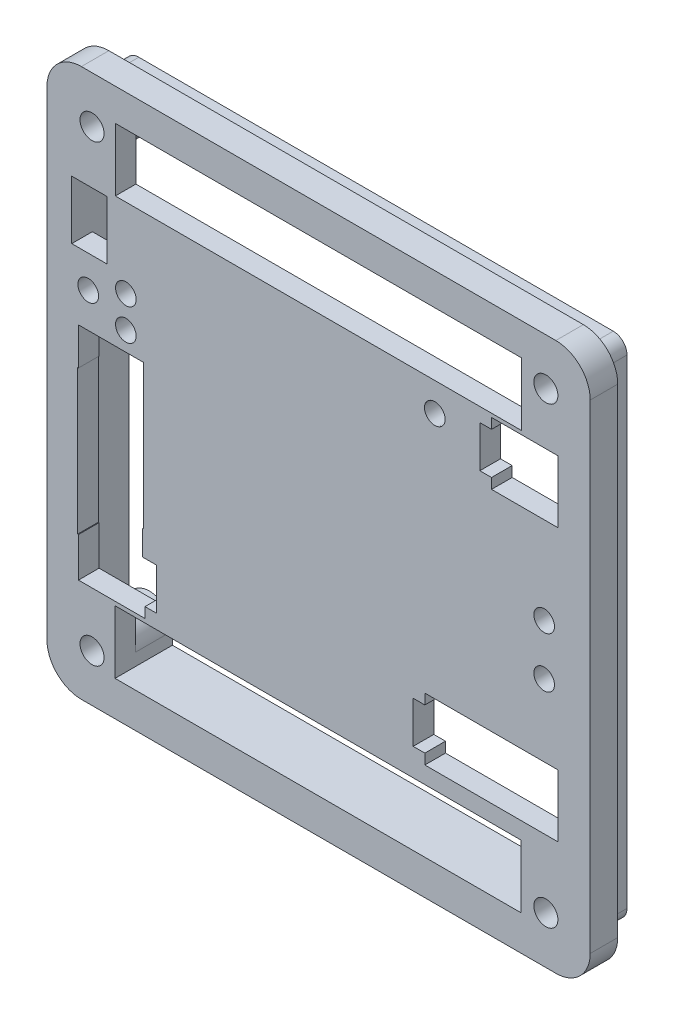
SolidWorks part; units mm, degrees
note: The reader was unsure of these and kept them because the rebuilt part matched: shared geometry of "Sketch9<3>".
ref_plane "Front Plane" through (0, 0, 0) normal (0, 0, 1) x (1, 0, 0)
ref_plane "Top Plane" through (0, 0, 0) normal (0, 1, 0) x (1, 0, 0)
ref_plane "Right Plane" through (0, 0, 0) normal (1, 0, 0) x (0, 0, -1)
sketch "Sketch1" plane through (0, 0, 0) normal (0, 0, 1) x (1, 0, 0)
  line L0 (188.15, -67.0655) -> (188.15, -73.1255)
  line L1 (127.6652, -102.1209) -> (127.6652, -110.3509)
  line L2 (127.6652, -110.3509) -> (137.1152, -110.3509)
  line L3 (137.1152, -110.3509) -> (137.1152, -89.3909)
  line L4 (127.9652, -97.6209) -> (127.9652, -102.1209) construction
  line L5 (137.1152, -89.3909) -> (127.6652, -89.3909)
  line L6 (127.6652, -89.3909) -> (127.6652, -97.6209)
  line L7 (127.6652, -97.6209) -> (127.6652, -102.1209)
  line L8 (128.2, -130.9) -> (197.2, -130.9)
  line L9 (202.2, -125.9) -> (202.2, -56.2)
  line L10 (197.2, -51.2) -> (128.2, -51.2)
  line L11 (123.2, -56.2) -> (123.2, -125.9)
  line L15 (188.15, -73.1255) -> (189.05, -73.1255)
  line L16 (189.05, -73.1255) -> (189.85, -73.1255)
  line L17 (189.85, -73.1255) -> (190.15, -73.1255)
  line L18 (190.15, -73.1255) -> (190.15, -74.3255)
  line L31 (127.9652, -102.1209) -> (127.9652, -110.0509)
  line L32 (160.412, -56.033) -> (133.432, -56.033) construction
  line L33 (133.432, -56.033) -> (133.432, -64.883) construction
  line L34 (133.432, -64.883) -> (191.892, -64.883) construction
  line L35 (191.892, -64.883) -> (191.892, -56.033) construction
  line L36 (191.892, -56.033) -> (164.912, -56.033) construction
  line L45 (190.15, -74.3255) -> (197.25, -74.3255)
  line L46 (197.25, -74.3255) -> (197.25, -65.8655)
  line L47 (197.25, -65.8655) -> (190.15, -65.8655)
  line L49 (190.15, -65.8655) -> (190.15, -67.0655)
  line L50 (190.15, -67.0655) -> (189.85, -67.0655)
  line L51 (189.85, -67.0655) -> (189.05, -67.0655)
  line L52 (189.05, -67.0655) -> (188.15, -67.0655)
  line L53 (133.132, -55.733) -> (192.192, -55.733)
  line L62 (188.15, -67.0655) -> (186.15, -67.0655)
  line L68 (188.15, -67.0655) -> (188.15, -73.1255)
  line L76 (188.15, -73.1255) -> (186.15, -73.1255)
  line L82 (186.15, -67.0655) -> (186.15, -73.1255)
  line L90 (127.9652, -110.0509) -> (136.8152, -110.0509)
  line L96 (136.8152, -110.0509) -> (136.8152, -89.6909)
  line L99 (136.8152, -89.6909) -> (127.9652, -89.6909)
  line L110 (127.9652, -89.6909) -> (127.9652, -97.6209)
  line L117 (127.9652, -97.6209) -> (237.023, -182.4747)
  line L118 (237.023, -182.4747) -> (233.3202, -188.1423)
  line L120 (233.3202, -188.1423) -> (228.0042, -184.6692)
  line L122 (228.0042, -184.6692) -> (237.871, -169.5667)
  line L123 (237.871, -169.5667) -> (243.1871, -173.0398)
  line L125 (131.6, -68.5) -> (131.6, -67.5) construction
  line L126 (131.6, -67.5) -> (131.65, -67.5) construction
  line L127 (131.65, -67.5) -> (131.65, -67) construction
  line L128 (131.65, -67) -> (131.6, -67) construction
  line L129 (131.6, -67) -> (131.6, -66) construction
  line L130 (131.6, -66) -> (130.1, -66) construction
  line L135 (130.1, -73.9) -> (131.6, -73.9) construction
  line L136 (131.6, -73.9) -> (131.6, -71.4) construction
  line L140 (127.1, -73.9) -> (129.3, -73.9) construction
  line L146 (129.3, -66) -> (127.1, -66) construction
  line L147 (127.1, -66) -> (127.1, -73.9) construction
  line L148 (188.45, -67.3655) -> (188.45, -72.8255) construction
  line L149 (188.45, -72.8255) -> (189.05, -72.8255) construction
  line L150 (189.05, -67.3655) -> (188.45, -67.3655) construction
  line L151 (189.05, -72.8255) -> (189.85, -72.8255) construction
  line L152 (189.85, -67.3655) -> (189.05, -67.3655) construction
  line L153 (189.85, -72.8255) -> (190.45, -72.8255) construction
  line L154 (131.6, -68.5) -> (131.6, -71.4) construction
  line L155 (190.45, -67.3655) -> (189.85, -67.3655) construction
  line L156 (190.45, -74.0255) -> (196.95, -74.0255) construction
  line L157 (196.95, -74.0255) -> (196.95, -66.1655) construction
  line L158 (196.95, -66.1655) -> (190.45, -66.1655) construction
  line L159 (190.45, -66.1655) -> (190.45, -67.3655) construction
  line L160 (130.1, -73.9) -> (129.3, -73.9) construction
  line L161 (190.45, -72.8255) -> (190.45, -74.0255) construction
  line L162 (178.75, -106.9275) -> (178.75, -112.3875) construction
  line L163 (178.75, -112.3875) -> (179.35, -112.3875) construction
  line L164 (179.35, -106.9275) -> (178.75, -106.9275) construction
  line L165 (179.35, -112.3875) -> (180.15, -112.3875) construction
  line L166 (180.15, -106.9275) -> (179.35, -106.9275) construction
  line L167 (180.15, -112.3875) -> (180.75, -112.3875) construction
  line L168 (129.3, -66) -> (130.1, -66) construction
  line L169 (180.75, -106.9275) -> (180.15, -106.9275) construction
  line L170 (180.75, -113.5875) -> (187.25, -113.5875) construction
  line L171 (187.25, -113.5875) -> (187.25, -105.7275) construction
  line L172 (187.25, -105.7275) -> (180.75, -105.7275) construction
  line L173 (180.75, -105.7275) -> (180.75, -106.9275) construction
  line L174 (243.1871, -173.0398) -> (239.4842, -178.7074)
  line L175 (180.75, -112.3875) -> (180.75, -113.5875) construction
  line L176 (188.45, -106.9275) -> (188.45, -112.3875) construction
  line L177 (188.45, -112.3875) -> (189.05, -112.3875) construction
  line L178 (189.05, -106.9275) -> (188.45, -106.9275) construction
  line L179 (189.05, -112.3875) -> (189.85, -112.3875) construction
  line L180 (189.85, -106.9275) -> (189.05, -106.9275) construction
  line L181 (189.85, -112.3875) -> (190.45, -112.3875) construction
  line L182 (133.432, -56.033) -> (191.892, -56.033) construction
  line L183 (190.45, -106.9275) -> (189.85, -106.9275) construction
  line L184 (190.45, -113.5875) -> (196.95, -113.5875) construction
  line L185 (196.95, -113.5875) -> (196.95, -105.7275) construction
  line L186 (196.95, -105.7275) -> (190.45, -105.7275) construction
  line L187 (190.45, -105.7275) -> (190.45, -106.9275) construction
  line L188 (133.432, -56.033) -> (133.432, -64.883) construction
  line L189 (190.45, -112.3875) -> (190.45, -113.5875) construction
  line L190 (135.45, -108.8275) -> (134.85, -108.8275) construction
  line L191 (133.432, -64.883) -> (191.892, -64.883) construction
  line L192 (134.85, -114.2875) -> (135.45, -114.2875) construction
  line L193 (136.85, -114.2875) -> (136.85, -108.8275) construction
  line L194 (136.85, -108.8275) -> (136.25, -108.8275) construction
  line L195 (136.25, -114.2875) -> (136.85, -114.2875) construction
  line L196 (136.25, -108.8275) -> (135.45, -108.8275) construction
  line L197 (135.45, -114.2875) -> (136.25, -114.2875) construction
  line L198 (134.85, -107.6275) -> (128.35, -107.6275) construction
  line L199 (128.35, -107.6275) -> (128.35, -115.4875) construction
  line L200 (128.35, -115.4875) -> (134.85, -115.4875) construction
  line L201 (134.85, -115.4875) -> (134.85, -114.2875) construction
  line L202 (191.892, -56.033) -> (191.892, -64.883) construction
  line L203 (134.85, -108.8275) -> (134.85, -107.6275) construction
  line L204 (164.875, -125.655) -> (191.855, -125.655) construction
  line L205 (191.855, -125.655) -> (191.855, -116.805) construction
  line L206 (191.855, -116.805) -> (133.395, -116.805) construction
  line L207 (133.395, -116.805) -> (133.395, -125.655) construction
  line L208 (133.395, -125.655) -> (160.375, -125.655) construction
  line L216 (160.375, -125.655) -> (164.875, -125.655) construction
  line L217 (160.412, -56.033) -> (164.875, -56.033) construction
  line L218 (133.132, -55.733) -> (133.132, -65.183)
  line L219 (133.132, -65.183) -> (192.192, -65.183)
  line L220 (192.192, -65.183) -> (192.192, -55.733)
  line L221 (239.4842, -178.7074) -> (127.9652, -102.1209)
  line L222 (126.8, -65.7) -> (126.8, -74.2)
  line L223 (126.8, -74.2) -> (129.3, -74.2)
  line L224 (130.1, -74.2) -> (129.3, -74.2)
  line L225 (130.1, -74.2) -> (131.9, -74.2)
  line L226 (131.9, -74.2) -> (131.9, -71.4)
  line L227 (131.9, -68.5) -> (131.9, -71.4)
  line L228 (131.9, -68.5) -> (131.9, -67.8)
  line L229 (131.9, -67.8) -> (131.95, -67.8)
  line L230 (131.95, -67.8) -> (131.95, -66.7)
  line L231 (131.95, -66.7) -> (131.9, -66.7)
  line L232 (131.9, -66.7) -> (131.9, -65.7)
  line L233 (131.9, -65.7) -> (130.1, -65.7)
  line L234 (129.3, -65.7) -> (130.1, -65.7)
  line L235 (129.3, -65.7) -> (126.8, -65.7)
  line L236 (128.05, -107.3275) -> (128.05, -115.7875)
  line L237 (128.05, -115.7875) -> (135.15, -115.7875)
  line L238 (135.15, -115.7875) -> (135.15, -114.5875)
  line L239 (135.15, -114.5875) -> (135.45, -114.5875)
  line L240 (135.45, -114.5875) -> (136.25, -114.5875)
  line L241 (136.25, -114.5875) -> (137.15, -114.5875)
  line L242 (137.15, -114.5875) -> (137.15, -108.5275)
  line L243 (137.15, -108.5275) -> (136.25, -108.5275)
  line L244 (136.25, -108.5275) -> (135.45, -108.5275)
  line L245 (135.45, -108.5275) -> (135.15, -108.5275)
  line L246 (135.15, -108.5275) -> (135.15, -107.3275)
  line L247 (135.15, -107.3275) -> (128.05, -107.3275)
  line L248 (180.45, -113.8875) -> (187.55, -113.8875)
  line L250 (187.55, -105.4275) -> (180.45, -105.4275)
  line L251 (180.45, -105.4275) -> (180.45, -106.6275)
  line L252 (180.45, -106.6275) -> (180.15, -106.6275)
  line L253 (180.15, -106.6275) -> (179.35, -106.6275)
  line L254 (179.35, -106.6275) -> (178.45, -106.6275)
  line L255 (178.45, -106.6275) -> (178.45, -112.6875)
  line L256 (178.45, -112.6875) -> (179.35, -112.6875)
  line L257 (179.35, -112.6875) -> (180.15, -112.6875)
  line L258 (180.15, -112.6875) -> (180.45, -112.6875)
  line L259 (180.45, -112.6875) -> (180.45, -113.8875)
  line L267 (190.15, -113.8875) -> (197.25, -113.8875)
  line L268 (197.25, -113.8875) -> (197.25, -105.4275)
  line L269 (197.25, -105.4275) -> (190.15, -105.4275)
  line L272 (192.155, -116.505) -> (133.095, -116.505)
  line L273 (133.095, -116.505) -> (133.095, -125.955)
  line L274 (133.095, -125.955) -> (160.375, -125.955)
  line L275 (160.375, -125.955) -> (164.875, -125.955)
  line L276 (164.875, -125.955) -> (192.155, -125.955)
  line L277 (192.155, -125.955) -> (192.155, -116.505)
  line L278 (187.55, -105.4275) -> (190.15, -105.4275)
  line L279 (190.15, -113.8875) -> (187.55, -113.8875)
  line L280 (127.9652, -102.1209) -> (127.9652, -110.0509) construction
  line L281 (190.15, -105.4275) -> (190.15, -106.6275) construction
  line L282 (190.15, -106.6275) -> (189.85, -106.6275) construction
  line L283 (189.85, -106.6275) -> (189.05, -106.6275) construction
  line L284 (189.05, -106.6275) -> (188.15, -106.6275) construction
  line L285 (188.15, -106.6275) -> (188.15, -112.6875) construction
  line L286 (190.15, -112.6875) -> (190.15, -113.8875) construction
  line L287 (189.85, -112.6875) -> (190.15, -112.6875) construction
  line L288 (189.05, -112.6875) -> (189.85, -112.6875) construction
  line L289 (188.15, -112.6875) -> (189.05, -112.6875) construction
  line L290 (187.55, -113.8875) -> (187.55, -105.4275) construction
  line L291 (178.45, -106.6275) -> (176.45, -106.6275)
  line L292 (178.45, -106.6275) -> (178.45, -112.6875)
  line L293 (178.45, -112.6875) -> (176.45, -112.6875)
  line L294 (176.45, -106.6275) -> (176.45, -112.6875)
  line L295 (137.15, -108.5275) -> (139.15, -108.5275)
  line L296 (137.15, -108.5275) -> (137.15, -114.5875)
  line L297 (137.15, -114.5875) -> (139.15, -114.5875)
  line L298 (139.15, -108.5275) -> (139.15, -114.5875)
  line L299 (127.9652, -110.0509) -> (136.8152, -110.0509) construction
  line L300 (192.192, -55.733) -> (164.912, -55.733) construction
  line L301 (160.412, -55.733) -> (133.132, -55.733) construction
  line L302 (136.8152, -110.0509) -> (136.8152, -89.6909) construction
  line L303 (136.8152, -89.6909) -> (127.9652, -89.6909) construction
  line L304 (127.9652, -89.6909) -> (127.9652, -97.6209) construction
  arc A8 (197.2, -130.9) -> (202.2, -125.9) centre (197.2, -125.9) ccw
  arc A9 (202.2, -56.2) -> (197.2, -51.2) centre (197.2, -56.2) ccw
  arc A10 (128.2, -51.2) -> (123.2, -56.2) centre (128.2, -56.2) ccw
  arc A11 (123.2, -125.9) -> (128.2, -130.9) centre (128.2, -125.9) ccw
  circle A14 centre (195.5, -94.675) radius 0.8 construction
  circle A15 centre (195.5, -87.325) radius 0.8 construction
  circle A16 centre (129.2, -78.87) radius 0.8 construction
  circle A17 centre (195.75, -124) radius 1.575 construction
  circle A18 centre (195.75, -58) radius 1.575 construction
  circle A19 centre (129.75, -58) radius 1.575 construction
  circle A21 centre (129.75, -124) radius 1.575 construction
  circle A22 centre (195.5, -94.675) radius 1.1
  circle A23 centre (195.5, -87.325) radius 1.1
  circle A24 centre (129.2, -78.87) radius 1.1
  circle A25 centre (129.75, -58) radius 1.75
  circle A26 centre (129.75, -124) radius 1.75
  circle A27 centre (195.75, -124) radius 1.75
  circle A28 centre (195.75, -58) radius 1.75
  dimension "D8" = 3.5
  dimension "D4" = 2
  dimension "D5" = 2
  dimension "D7" = 2
  dimension "D1" = 0
  dimension "D2" = 0.3
  dimension "D3" = 0.3
  dimension "D6" = 0.3
extrude "Boss-Extrude1" add sketch "Sketch1" along normal blind 3 contours L11 A11 L8 A8 L9 A9 L10 A10 A28 A27 A26 A25 A24 A23 A22 L295 L298 L297 L241 L240 L239 L238 L237 L236 L247 L246 L245 L244 L243 L82 L62 L52 L51 L50 L49 L47 L46 L45 L18 L17 L16 L15
sketch "Sketch2" plane through (0, 0, 0) normal (0, 0, -1) x (-1, 0, 0)
  line L1 (-192.192, -58) -> (-192.192, -55.733)
  line L3 (-133.132, -58) -> (-133.132, -55.733)
  line L4 (-123.2, -125.9) -> (-123.2, -56.2)
  line L5 (-128.2, -51.2) -> (-197.2, -51.2)
  line L6 (-202.2, -56.2) -> (-202.2, -125.9)
  line L7 (-197.2, -130.9) -> (-128.2, -130.9)
  line L8 (-123.2, -125.9) -> (-123.2, -116.505)
  line L9 (-128.2, -51.2) -> (-133.132, -51.2)
  line L10 (-202.2, -56.2) -> (-202.2, -65.183)
  line L11 (-197.2, -130.9) -> (-192.155, -130.9)
  line L13 (-133.095, -124) -> (-133.095, -125.955)
  line L15 (-192.155, -124) -> (-192.155, -125.955)
  line L16 (-192.192, -51.2) -> (-197.2, -51.2)
  line L17 (-202.2, -116.505) -> (-202.2, -125.9)
  line L18 (-123.2, -65.183) -> (-123.2, -56.2)
  line L19 (-133.095, -130.9) -> (-128.2, -130.9)
  line L20 (-192.192, -55.733) -> (-133.132, -55.733)
  line L21 (-127.0358, -125.955) -> (-126.8, -125.955)
  line L23 (-126.8, -122.4231) -> (-126.8, -59.6539)
  line L24 (-126.8, -125.955) -> (-126.8, -125.5769)
  line L26 (-197.25, -61.2264) -> (-197.25, -120.7329)
  line L27 (-202.2, -65.183) -> (-202.2, -116.505)
  line L28 (-123.2, -65.183) -> (-123.2, -116.505)
  line L29 (-192.155, -125.955) -> (-133.095, -125.955)
  line L30 (-192.155, -130.9) -> (-133.095, -130.9)
  line L31 (-192.192, -51.2) -> (-133.132, -51.2)
  arc A0 (-197.25, -61.2264) -> (-192.192, -58) centre (-195.75, -58) ccw
  arc A2 (-127.0358, -125.955) -> (-126.8, -125.5769) centre (-129.75, -124) ccw
  arc A3 (-133.132, -58) -> (-126.8, -59.6539) centre (-129.75, -58) ccw
  arc A4 (-123.2, -56.2) -> (-128.2, -51.2) centre (-128.2, -56.2) ccw
  arc A5 (-197.2, -51.2) -> (-202.2, -56.2) centre (-197.2, -56.2) ccw
  arc A6 (-202.2, -125.9) -> (-197.2, -130.9) centre (-197.2, -125.9) ccw
  arc A7 (-128.2, -130.9) -> (-123.2, -125.9) centre (-128.2, -125.9) ccw
  arc A8 (-123.2, -56.2) -> (-128.2, -51.2) centre (-128.2, -56.2) ccw
  arc A9 (-197.2, -51.2) -> (-202.2, -56.2) centre (-197.2, -56.2) ccw
  arc A10 (-202.2, -125.9) -> (-197.2, -130.9) centre (-197.2, -125.9) ccw
  arc A11 (-128.2, -130.9) -> (-123.2, -125.9) centre (-128.2, -125.9) ccw
  arc A12 (-192.155, -124) -> (-197.25, -120.7329) centre (-195.75, -124) ccw
  arc A13 (-126.8, -122.4231) -> (-133.095, -124) centre (-129.75, -124) ccw
  circle A15 centre (-195.75, -58) radius 1.75 construction
  circle A16 centre (-129.75, -58) radius 1.75 construction
  circle A17 centre (-129.75, -124) radius 1.75 construction
  circle A18 centre (-195.75, -124) radius 1.75 construction
  circle A19 centre (-195.75, -58) radius 1.75
  circle A20 centre (-129.75, -58) radius 1.75
  circle A21 centre (-129.75, -124) radius 1.75
  circle A22 centre (-195.75, -124) radius 1.75
  point P39 (-197.25, -91.05)
  point P42 (-162.7, -55.733)
  point P45 (-126.8, -88.6775)
  point P52 (-162.7, -125.955)
  dimension "D1" = 0
extrude "Boss-Extrude2" add sketch "Sketch2" along normal blind 6.15
sketch "Sketch3" plane through (0, -51.2, 0) normal (0, 1, 0) x (1, 0, 0)
  line L0 (197.2, -3) -> (128.2, -3) construction
  line L1 (45.1071, 1) -> (280.2929, 1)
  line L2 (45.1071, 1) -> (45.1071, -7)
  line L3 (45.1071, -7) -> (280.2929, -7)
  line L4 (280.2929, 1) -> (280.2929, -7)
  line L5 (45.1071, 1) -> (280.2929, -7) construction
  line L6 (45.1071, -7) -> (280.2929, 1) construction
  point P0 (162.7, -3)
  dimension "D1" = 4
sketch "Sketch4" plane through (0, 0, -6.15) normal (0, 0, 1) x (1, 0, 0)
  line L8 (96.5451, -180.9483) -> (273.7958, -180.9483)
  line L9 (96.5451, -180.9483) -> (96.5451, -1.9529)
  line L10 (96.5451, -1.9529) -> (273.7958, -1.9529)
  line L17 (126.2, -56.2) -> (126.2, -125.9)
  line L18 (197.2, -54.2) -> (128.2, -54.2)
  line L19 (199.2, -125.9) -> (199.2, -56.2)
  line L20 (128.2, -127.9) -> (197.2, -127.9)
  line L21 (126.2, -56.2) -> (126.2, -125.9)
  line L22 (197.2, -54.2) -> (128.2, -54.2)
  line L23 (199.2, -125.9) -> (199.2, -56.2)
  line L24 (128.2, -127.9) -> (197.2, -127.9)
  line L25 (273.7958, -180.9483) -> (273.7958, -1.9529)
  arc A8 (126.2, -125.9) -> (128.2, -127.9) centre (128.2, -125.9) ccw
  arc A9 (128.2, -54.2) -> (126.2, -56.2) centre (128.2, -56.2) ccw
  arc A10 (199.2, -56.2) -> (197.2, -54.2) centre (197.2, -56.2) ccw
  arc A11 (197.2, -127.9) -> (199.2, -125.9) centre (197.2, -125.9) ccw
  arc A12 (126.2, -125.9) -> (128.2, -127.9) centre (128.2, -125.9) ccw
  arc A13 (128.2, -54.2) -> (126.2, -56.2) centre (128.2, -56.2) ccw
  arc A14 (199.2, -56.2) -> (197.2, -54.2) centre (197.2, -56.2) ccw
  arc A15 (197.2, -127.9) -> (199.2, -125.9) centre (197.2, -125.9) ccw
  dimension "D1" = 3
extrude "Cut-Extrude2" cut sketch "Sketch4" along normal blind 5.15
sketch "Sketch5" plane through (0, 0, 3) normal (0, 0, 1) x (1, 0, 0)
  line L0 (128.06, -92.17) -> (128.06, -96.67) construction
  line L1 (127.76, -92.17) -> (127.76, -96.67)
  line L2 (127.76, -96.67) -> (127.76, -104.9)
  line L3 (127.76, -104.9) -> (137.21, -104.9)
  line L4 (137.21, -104.9) -> (137.21, -83.94)
  line L5 (137.21, -83.94) -> (127.76, -83.94)
  line L6 (127.76, -83.94) -> (127.76, -92.17)
  line L12 (128.06, -96.67) -> (128.06, -104.6)
  line L13 (128.06, -104.6) -> (136.91, -104.6)
  line L14 (136.91, -104.6) -> (136.91, -84.24)
  line L15 (136.91, -84.24) -> (128.06, -84.24)
  line L16 (128.06, -84.24) -> (128.06, -92.17)
  line L17 (128.06, -92.17) -> (129.31, -92.17)
  line L18 (129.31, -92.17) -> (129.31, -85.4)
  line L19 (129.31, -85.4) -> (135.66, -85.4)
  line L20 (135.66, -85.4) -> (135.66, -103.44)
  line L21 (135.66, -103.44) -> (129.31, -103.44)
  line L22 (129.31, -103.44) -> (129.31, -96.67)
  line L23 (129.31, -96.67) -> (128.06, -96.67)
  line L24 (128.06, -96.67) -> (128.06, -104.6) construction
  line L25 (128.06, -104.6) -> (136.91, -104.6) construction
  line L26 (136.91, -104.6) -> (136.91, -84.24) construction
  line L27 (136.91, -84.24) -> (128.06, -84.24) construction
  line L28 (128.06, -84.24) -> (128.06, -92.17) construction
  dimension "D1" = 0
  dimension "D2" = 0.3
extrude "Cut-Extrude3" cut sketch "Sketch5" against normal through all both and the other way through all
sketch "Sketch6" plane through (0, 0, 3) normal (0, 0, 1) x (1, 0, 0)
  line L3 (190.15, -65.8655) -> (189.65, -65.8655)
  line L4 (190.15, -65.8655) -> (190.15, -74.3255)
  line L5 (190.15, -74.3255) -> (189.65, -74.3255)
  line L6 (189.65, -65.8655) -> (189.65, -74.3255)
  line L7 (180.45, -105.4275) -> (179.95, -105.4275)
  line L8 (180.45, -105.4275) -> (180.45, -113.8875)
  line L9 (180.45, -113.8875) -> (179.95, -113.8875)
  line L10 (179.95, -105.4275) -> (179.95, -113.8875)
  line L11 (135.15, -115.7875) -> (135.65, -115.7875)
  line L12 (135.15, -115.7875) -> (135.15, -107.6212)
  line L13 (135.15, -107.6212) -> (135.65, -107.6212)
  line L14 (135.65, -115.7875) -> (135.65, -107.6212)
  dimension "D1" = 0.5
  dimension "D2" = 0.5
  dimension "D3" = 0.5
extrude "Cut-Extrude4" cut sketch "Sketch6" against normal through all contours L11 L14 L13 L12 | L7 L10 L9 L8 | L3 L6 L5 L4
sketch "Sketch8" plane through (0, 0, 3) normal (0, 0, 1) x (1, 0, 0)
  line L0 (189.65, -65.8655) -> (189.65, -74.3255) construction
  line L1 (179.95, -105.4275) -> (179.95, -113.8875) construction
  line L2 (135.65, -114.5875) -> (135.65, -107.8878)
  line L3 (189.35, -74.6255) -> (197.55, -74.6255)
  line L4 (179.95, -113.8875) -> (197.25, -113.8875) construction
  line L5 (197.25, -113.8875) -> (197.25, -105.4275) construction
  line L6 (197.25, -105.4275) -> (179.95, -105.4275) construction
  line L7 (189.65, -74.3255) -> (197.25, -74.3255) construction
  line L8 (197.25, -74.3255) -> (197.25, -65.8655) construction
  line L9 (197.25, -65.8655) -> (189.65, -65.8655) construction
  line L10 (179.95, -113.8875) -> (197.25, -113.8875) construction
  line L11 (197.25, -113.8875) -> (197.25, -105.4275) construction
  line L12 (197.25, -105.4275) -> (179.95, -105.4275) construction
  line L13 (189.65, -74.3255) -> (197.25, -74.3255) construction
  line L14 (197.25, -74.3255) -> (197.25, -65.8655) construction
  line L15 (197.25, -65.8655) -> (189.65, -65.8655) construction
  line L16 (197.55, -74.6255) -> (197.55, -65.5655)
  line L17 (135.65, -115.7875) -> (128.0768, -115.7875) construction
  line L18 (135.65, -115.7875) -> (135.65, -106.7673) construction
  line L19 (135.65, -106.7673) -> (128.0768, -106.7673) construction
  line L20 (128.0768, -115.7875) -> (128.0768, -106.7673) construction
  line L21 (197.55, -65.5655) -> (189.35, -65.5655)
  line L22 (189.35, -65.5655) -> (189.35, -74.6255)
  line L24 (179.65, -114.1875) -> (197.55, -114.1875)
  line L25 (197.55, -114.1875) -> (197.55, -105.1275)
  line L26 (197.55, -105.1275) -> (179.65, -105.1275)
  line L27 (179.65, -105.1275) -> (179.65, -114.1875)
  line L28 (135.95, -116.0875) -> (135.95, -106.4673)
  line L29 (135.95, -106.4673) -> (127.7768, -106.4673)
  line L30 (127.7768, -116.0875) -> (127.7768, -106.4673)
  line L31 (135.95, -116.0875) -> (127.7768, -116.0875)
  dimension "D1" = 0.3
  dimension "D2" = 0.3
  dimension "D3" = 0.3
extrude "Cut-Extrude5" cut sketch "Sketch8" against normal through all
sketch "Sketch9" plane through (0, 0, 3) normal (0, 0, 1) x (1, 0, 0)
  line L1 (192.192, -65.183) -> (192.192, -55.733) construction
  line L2 (133.132, -55.733) -> (192.192, -55.733)
  line L3 (133.132, -55.733) -> (133.132, -55.883)
  line L4 (133.132, -55.883) -> (192.192, -55.883)
  line L5 (192.192, -55.733) -> (192.192, -55.883)
  line L6 (133.132, -55.733) -> (133.132, -65.183) construction
  line L7 (192.192, -65.183) -> (133.132, -65.183)
  line L8 (192.192, -65.183) -> (192.192, -65.033)
  line L9 (192.192, -65.033) -> (133.132, -65.033)
  line L10 (133.132, -65.183) -> (133.132, -65.033)
  line L11 (192.155, -125.955) -> (192.155, -116.505) construction
  line L12 (133.095, -116.505) -> (192.155, -116.505)
  line L13 (133.095, -116.505) -> (133.095, -116.655)
  line L14 (133.095, -116.655) -> (192.155, -116.655)
  line L15 (192.155, -116.505) -> (192.155, -116.655)
  line L16 (133.095, -116.505) -> (133.095, -125.955) construction
  line L17 (192.155, -125.955) -> (133.095, -125.955)
  line L18 (192.155, -125.955) -> (192.155, -125.805)
  line L19 (192.155, -125.805) -> (133.095, -125.805)
  line L20 (133.095, -125.955) -> (133.095, -125.805)
  dimension "D1" = 0.15
extrude "Boss-Extrude3" add sketch "Sketch9" against normal up to surface (9.15 mm away) contours L2 L5 L4 L3 | L19 L20 L17 L18
extrude "Boss-Extrude4" add sketch "Sketch9<3>" against normal up to surface (3 mm away) contours L10 L7 L8 L9 | L15 L12 L13 L14 up to face at (166.2229, -85.5061, 0)
sketch "Sketch9<3>" plane through (0, 0, 3) normal (0, 0, 1) x (1, 0, 0) same geometry as "Sketch9"
sketch "Sketch10" plane through (0, 0, 0) normal (0, 0, -1) x (-1, 0, 0)
  circle A2 centre (-195.5, -94.675) radius 1.5
  circle A3 centre (-195.5, -87.325) radius 1.5
  circle A4 centre (-129.2, -78.87) radius 1.5
  dimension "D1" = 3
extrude "Cut-Extrude6" cut sketch "Sketch10" against normal through all
sketch "Sketch11" plane through (0, -54.2, 0) normal (0, 1, 0) x (1, 0, 0)
  line L0 (199.2, 1) -> (199.2, 6.15) construction
  line L1 (126.2, 6.15) -> (199.2, 6.15)
  line L2 (126.2, 6.15) -> (126.2, 5.35)
  line L3 (126.2, 5.35) -> (199.2, 5.35)
  line L4 (199.2, 6.15) -> (199.2, 5.35)
  dimension "D1" = 0.8
extrude "Cut-Extrude7" cut sketch "Sketch11" against normal through all both and the other way through all
sketch "Sketch12" plane through (0, 0, 3) normal (0, 0, 1) x (1, 0, 0)
  arc A0 (133.17, -81.17) -> (136.17, -81.17) centre (134.67, -81.17) ccw construction
  arc A1 (136.17, -81.17) -> (133.17, -81.17) centre (134.67, -81.17) ccw construction
  arc A2 (136.17, -76.57) -> (133.17, -76.57) centre (134.67, -76.57) ccw construction
  arc A3 (133.17, -76.57) -> (136.17, -76.57) centre (134.67, -76.57) ccw construction
  arc A4 (133.17, -81.17) -> (136.17, -81.17) centre (134.67, -81.17) ccw
  arc A5 (136.17, -81.17) -> (133.17, -81.17) centre (134.67, -81.17) ccw
  arc A6 (136.17, -76.57) -> (133.17, -76.57) centre (134.67, -76.57) ccw
  arc A7 (133.17, -76.57) -> (136.17, -76.57) centre (134.67, -76.57) ccw
  spline S0 degree 3 poles (181.1, -69.3963) (181.1, -69.0037) (181.061, -68.8074) (180.9107, -68.4446) (180.7995, -68.2782) (180.5218, -68.0005) (180.3554, -67.8893) (179.9926, -67.739) (179.7963, -67.7) (179.4037, -67.7) (179.2074, -67.739) (178.8446, -67.8893) (178.6782, -68.0005) (178.4005, -68.2782) (178.2893, -68.4446) (178.139, -68.8074) (178.1, -69.0037) (178.1, -69.3963) (178.139, -69.5926) (178.2893, -69.9554) (178.4005, -70.1218) (178.6782, -70.3995) (178.8446, -70.5107) (179.2074, -70.661) (179.4037, -70.7) (179.7963, -70.7) (179.9926, -70.661) (180.3554, -70.5107) (180.5218, -70.3995) (180.7995, -70.1218) (180.9107, -69.9554) (181.061, -69.5926) (181.1, -69.3963) (181.1, -69.0037) (181.061, -68.8074) knots -0.0625 -0.0625 0 0 0.0625 0.0625 0.125 0.125 0.1875 0.1875 0.25 0.25 0.3125 0.3125 0.375 0.375 0.4375 0.4375 0.5 0.5 0.5625 0.5625 0.625 0.625 0.6875 0.6875 0.75 0.75 0.8125 0.8125 0.875 0.875 0.9375 0.9375 1 1 1.0625 1.0625 1.125 only from (181.1, -69.2) to (181.1, -69.2) construction
  spline S1 degree 3 poles (181.1, -69.3963) (181.1, -69.0037) (181.061, -68.8074) (180.9107, -68.4446) (180.7995, -68.2782) (180.5218, -68.0005) (180.3554, -67.8893) (179.9926, -67.739) (179.7963, -67.7) (179.4037, -67.7) (179.2074, -67.739) (178.8446, -67.8893) (178.6782, -68.0005) (178.4005, -68.2782) (178.2893, -68.4446) (178.139, -68.8074) (178.1, -69.0037) (178.1, -69.3963) (178.139, -69.5926) (178.2893, -69.9554) (178.4005, -70.1218) (178.6782, -70.3995) (178.8446, -70.5107) (179.2074, -70.661) (179.4037, -70.7) (179.7963, -70.7) (179.9926, -70.661) (180.3554, -70.5107) (180.5218, -70.3995) (180.7995, -70.1218) (180.9107, -69.9554) (181.061, -69.5926) (181.1, -69.3963) (181.1, -69.0037) (181.061, -68.8074) knots -0.0625 -0.0625 0 0 0.0625 0.0625 0.125 0.125 0.1875 0.1875 0.25 0.25 0.3125 0.3125 0.375 0.375 0.4375 0.4375 0.5 0.5 0.5625 0.5625 0.625 0.625 0.6875 0.6875 0.75 0.75 0.8125 0.8125 0.875 0.875 0.9375 0.9375 1 1 1.0625 1.0625 1.125 only from (181.1, -69.2) to (181.1, -69.2)
extrude "Cut-Extrude8" cut sketch "Sketch12" against normal blind 10
sketch "Sketch13" plane through (0, 0, 3) normal (0, 0, 1) x (1, 0, 0)
  line L0 (197.55, -65.5655) -> (189.35, -65.5655) construction
  line L1 (189.35, -74.6255) -> (187.85, -74.6255)
  line L2 (189.35, -74.6255) -> (189.35, -65.5655)
  line L3 (189.35, -65.5655) -> (187.85, -65.5655)
  line L4 (187.85, -74.6255) -> (187.85, -65.5655)
  line L5 (137.1152, -108.5275) -> (139.15, -108.5275) construction
  line L6 (135.95, -116.0875) -> (137.45, -116.0875)
  line L7 (135.95, -116.0875) -> (135.95, -108.5275)
  line L8 (135.95, -108.5275) -> (137.45, -108.5275)
  line L9 (137.45, -116.0875) -> (137.45, -108.5275)
  line L10 (197.55, -105.1275) -> (179.65, -105.1275) construction
  line L11 (179.65, -114.1875) -> (178.15, -114.1875)
  line L12 (179.65, -114.1875) -> (179.65, -105.1275)
  line L13 (179.65, -105.1275) -> (178.15, -105.1275)
  line L14 (178.15, -114.1875) -> (178.15, -105.1275)
  dimension "D1" = 1.5
  dimension "D2" = 1.5
  dimension "D3" = 1.5
extrude "Cut-Extrude9" cut sketch "Sketch13" against normal blind 10
